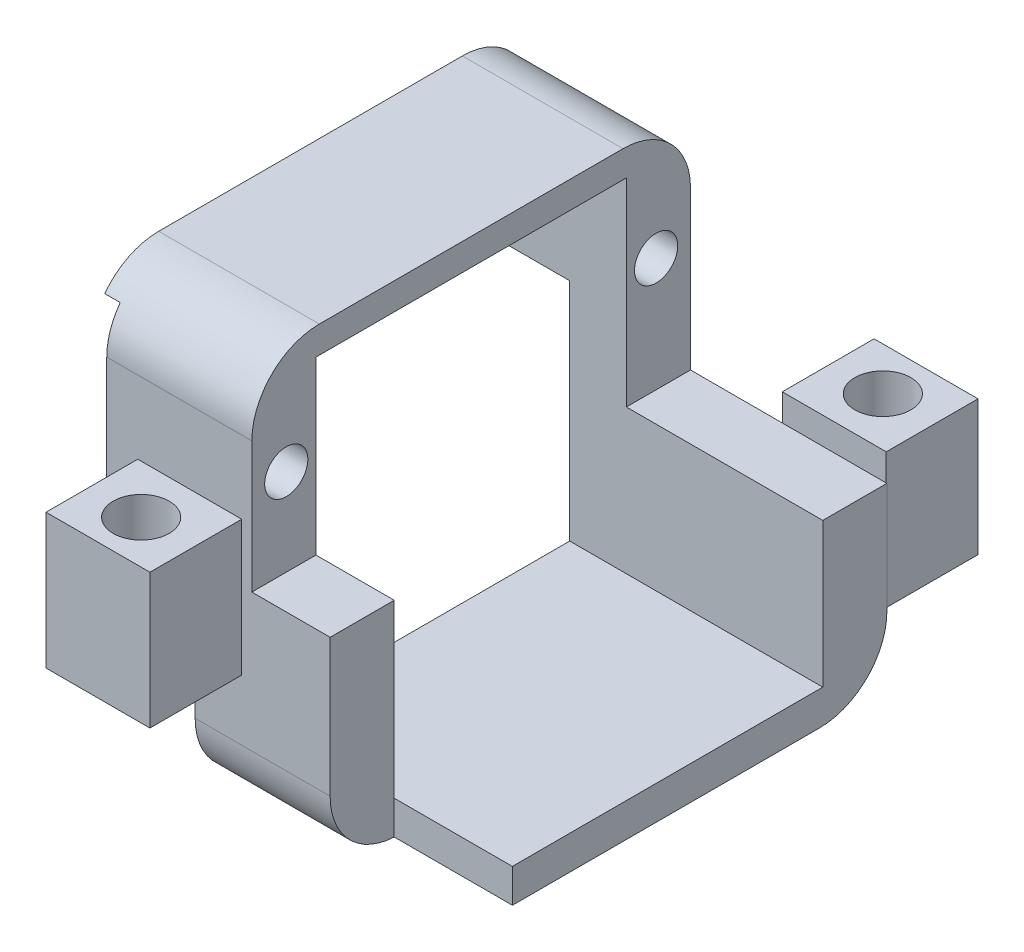
SolidWorks part; units mm, degrees
ref_plane "Front Plane" through (0, 0, 0) normal (0, 0, 1) x (1, 0, 0)
ref_plane "Top Plane" through (0, 0, 0) normal (0, 1, 0) x (1, 0, 0)
ref_plane "Right Plane" through (0, 0, 0) normal (1, 0, 0) x (0, 0, -1)
sketch "Sketch1" plane through (0, 0, 0) normal (0, 1, 0) x (1, 0, 0)
  line L0 (-1.1, 16.25) -> (-1.1, 11.5)
  line L1 (-17.65, -16.25) -> (17.65, -16.25)
  line L2 (-17.65, -16.25) -> (-17.65, 16.25)
  line L3 (-17.65, 16.25) -> (17.65, 16.25)
  line L4 (17.65, -16.25) -> (17.65, 16.25)
  line L5 (-17.65, -16.25) -> (17.65, 16.25) construction
  line L6 (-17.65, 16.25) -> (17.65, -16.25) construction
  line L7 (-1.1, 11.5) -> (17.65, 11.5)
  line L8 (-1.1, -16.25) -> (-1.1, -11.5)
  line L9 (-1.1, -11.5) -> (17.65, -11.5)
  line L10 (-1.1, 11.5) -> (-1.1, -11.5) construction
  line L11 (8.9, -11.5) -> (8.9, -16.25)
  line L12 (-8.8, 16.25) -> (-8.8, 11.5)
  line L13 (-8.8, 11.5) -> (-3.8, 11.5)
  line L14 (-3.8, 11.5) -> (-3.8, 16.25)
  line L15 (-3.8, -16.25) -> (-3.8, -11.5)
  line L16 (-3.8, -11.5) -> (-8.8, -11.5)
  line L17 (-8.8, -11.5) -> (-8.8, -16.25)
  line L18 (-8.8, 11.5) -> (-8.8, -11.5)
  line L19 (17.6, 16.25) -> (17.6, 23.05)
  line L20 (17.6, 23.05) -> (9.9, 23.05)
  line L21 (9.9, 23.05) -> (9.9, 16.25)
  line L22 (-5.35, -16.25) -> (-5.35, -23.05)
  line L23 (-5.35, -23.05) -> (2.35, -23.05)
  line L24 (2.35, -23.05) -> (2.35, -16.25)
  line L28 (-1.1, 11.5) -> (-1.1, -11.5)
  circle A0 centre (13.75, 19.85) radius 2.075
  circle A2 centre (-1.5, -19.85) radius 2.075
  point P0 (0, 0)
  point P11 (-1.1, 0)
  point P31 (13.75, 23.05)
  point P45 (-1.5, -23.05)
  dimension "D11" = 4.15
  dimension "D19" = 4.15
  dimension "D1" = 32.5
  dimension "D2" = 23
  dimension "D3" = 8.75
  dimension "D4" = 10
  dimension "D5" = 16.55
  dimension "D6" = 2.7
  dimension "D7" = 5
  dimension "D8" = 13.75
  dimension "D9" = 7.7
  dimension "D10" = 6.8
  dimension "D12" = 1.5
  dimension "D13" = 19.85
  dimension "D16" = 7.7
  dimension "D17" = 6.8
  dimension "D20" = 19.85
extrude "Boss-Extrude1" add sketch "Sketch1" against normal blind 2.5 contours L7 L28 L9 L4 | L0 L7 L4 L3 | L11 L9 L8 L1 region at (8.275, 0, -13.875) region at (8.275, 0, 0) region at (3.9, 0, 13.875)
extrude "Boss-Extrude2" add sketch "Sketch1<3>" along normal blind 12.7 contours L0 L7 L4 L3 | L11 L9 L8 L1 region at (8.275, 0, -13.875) region at (3.9, 0, 13.875)
sketch "Sketch1<3>" plane through (0, 0, 0) normal (0, 1, 0) x (1, 0, 0) same geometry as "Sketch1"
sketch "Sketch3" plane through (0, 0, 0) normal (0, 1, 0) x (1, 0, 0)
  line L0 (3.1, 16.25) -> (3.1, 11.5)
  line L1 (-17.65, 16.25) -> (17.65, 16.25) construction
  line L2 (-1.1, 11.5) -> (17.65, 11.5) construction
  line L3 (3.1, 11.5) -> (-17.65, 11.5)
  line L4 (-17.65, -16.25) -> (-17.65, 16.25) construction
  line L5 (3.1, -16.25) -> (3.1, -11.5)
  line L6 (-17.65, -16.25) -> (17.65, -16.25) construction
  line L7 (-1.1, -11.5) -> (17.65, -11.5) construction
  line L8 (3.1, -11.5) -> (-17.65, -11.5)
  line L9 (3.1, 11.5) -> (3.1, -11.5)
  line L10 (-7.65, -11.5) -> (-7.65, -16.275)
  line L11 (3.1, 16.25) -> (-17.65, 16.25)
  line L12 (-17.65, 16.25) -> (-17.65, 11.5)
  line L13 (-17.65, -11.5) -> (-17.65, -16.25)
  line L14 (-17.65, -16.25) -> (3.1, -16.25)
  line L15 (-8.8, 11.5) -> (-8.8, -11.5)
  line L16 (-8.8, 11.5) -> (-8.8, 16.25)
  line L17 (-8.8, -11.5) -> (-8.8, -16.25)
  dimension "D1" = 20.75
  dimension "D2" = 10
extrude "Boss-Extrude3" add sketch "Sketch3" along normal blind 12.7 from surface contours L11 L12 L3 L0 | L10 L14 L5 L8 region at (-2.85, 0, -13.875) region at (-2.275, 0, 13.875) starting at face at (8.275, 12.7, -13.875)
extrude "Boss-Extrude4" add sketch "Sketch3<3>" along normal blind 2 from surface contours L16 L3 L0 L11 | L3 L15 L8 L9 | L10 L14 L5 L8 | L8 L17 L14 L10 region at (-2.85, 0, -13.875) region at (-2.85, 0, 0) region at (-2.275, 0, 13.875) region at (-8.225, 0, 13.875) starting at face at (-2.275, 25.4, 13.875)
sketch "Sketch3<3>" plane through (0, 0, 0) normal (0, 1, 0) x (1, 0, 0) same geometry as "Sketch3"
sketch "Sketch2" plane through (0, 0, 0) normal (1, 0, 0) x (0, 0, -1)
  line L0 (13.7, 6.45) -> (-13.7, 6.45) construction
  line L1 (-13.7, 19.15) -> (13.7, 19.15) construction
  circle A0 centre (13.7, 6.45) radius 1.6
  circle A1 centre (-13.7, 6.45) radius 1.6
  circle A2 centre (-13.7, 19.15) radius 1.6
  circle A3 centre (13.7, 19.15) radius 1.6
  point P4 (0, 6.45)
  dimension "D1" = 3.2
  dimension "D2" = 3.2
  dimension "D6" = 3.2
  dimension "D7" = 3.2
  dimension "D3" = 27.4
  dimension "D4" = 6.45
  dimension "D5" = 6.45
extrude "Cut-Extrude1" cut sketch "Sketch2" along normal blind 8 from surface contours A1 | A0 region at (0, 6.45, -13.7) region at (0, 6.45, 13.7) starting at face at (-1.1, 5.725, 0)
extrude "Cut-Extrude2" cut sketch "Sketch2<3>" against normal blind 8 from surface contours A3 | A2 region at (0, 19.15, 13.7) region at (0, 19.15, -13.7) starting at face at (3.1, 19.55, 0)
sketch "Sketch2<3>" plane through (0, 0, 0) normal (1, 0, 0) x (0, 0, -1) same geometry as "Sketch2"
extrude "Boss-Extrude5" add sketch "Sketch1<4>" along normal blind 10 from offset 7 contours L23 L24 L1 L22 A2 region at (0.625, 0, 16.3527)
sketch "Sketch1<4>" plane through (0, 0, 0) normal (0, 1, 0) x (1, 0, 0) same geometry as "Sketch1"
extrude "Boss-Extrude6" add sketch "Sketch1<7>" against normal blind 10 from surface contours L20 L21 L3 L19 A0 region at (10.0027, 0, -19.65) starting at face at (10.375, 12.7, -13.875)
sketch "Sketch1<7>" plane through (0, 0, 0) normal (0, 1, 0) x (1, 0, 0) same geometry as "Sketch1"
fillet "Fillet1" radius 5 4 edges at (3.9, -2.5, 16.25) (-2.85, 27.4, 16.25) (8.275, -2.5, -16.25) (-2.85, 27.4, -16.25)
sketch "Sketch5" plane through (0, 0, 0) normal (0, 1, 0) x (1, 0, 0)
  line L1 (17.65, 16.25) -> (3.1, 16.25)
  line L2 (17.65, 16.25) -> (17.65, 11.5)
  line L3 (17.65, 11.5) -> (3.1, 11.5)
  line L4 (3.1, 16.25) -> (3.1, 11.5)
extrude "Cut-Extrude3" cut sketch "Sketch5" against normal blind 2 from surface starting at face at (12.0625, 12.7, -16.7625)
sketch "Sketch6" plane through (0, 0, 0) normal (0, 1, 0) x (1, 0, 0)
  line L1 (-8.8, 11.5) -> (-1.1, 11.5)
  line L2 (-8.8, 11.5) -> (-8.8, 16.25)
  line L3 (-8.8, 16.25) -> (-1.1, 16.25)
  line L4 (-1.1, 11.5) -> (-1.1, 16.25)
extrude "Cut-Extrude4" cut sketch "Sketch6" along normal blind 4 from surface starting at face at (-4.95, 12.7, -13.875)
